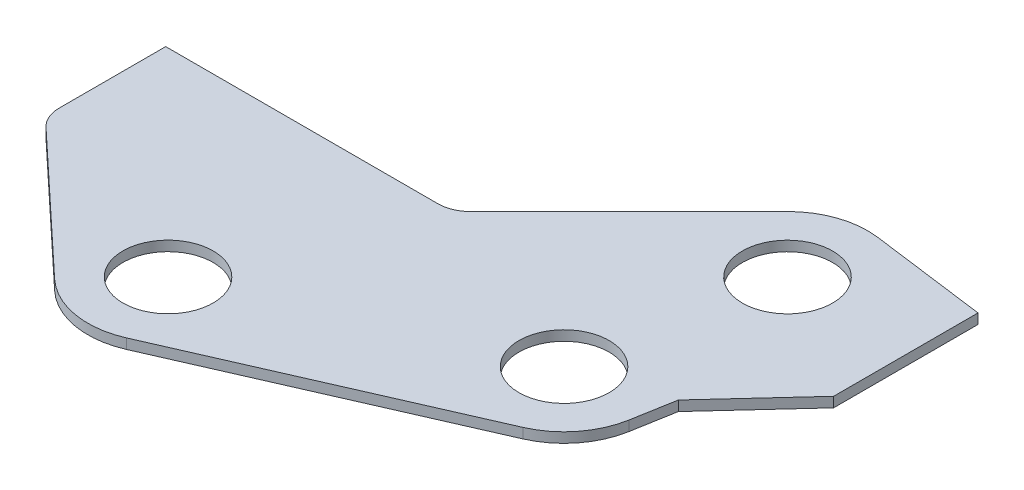
SolidWorks part; units mm, degrees
ref_plane "Front Plane" through (0, 0, 0) normal (0, 0, 1) x (1, 0, 0)
ref_plane "Top Plane" through (0, 0, 0) normal (0, 1, 0) x (1, 0, 0)
ref_plane "Right Plane" through (0, 0, 0) normal (1, 0, 0) x (0, 0, -1)
sketch "Sketch1" plane through (0, 0, 0) normal (0, 1, 0) x (1, 0, 0)
  line L1 (-62.0695, -79.8953) -> (25.163, -41.6958)
  line L5 (39.9361, -22.8907) -> (42.2711, -9.5867)
  line L6 (42.2711, -9.5867) -> (65.827, 16.0128)
  line L9 (7.8649, 59.3767) -> (-32.6636, 18.8643)
  line L12 (-135.7857, -31.9357) -> (-135.7857, 6.1643)
  line L15 (-32.6636, 18.8643) -> (-45.3687, 6.1643)
  line L16 (-135.7857, 6.1643) -> (-45.3687, 6.1643)
  line L17 (-135.7857, -31.9357) -> (-89.6201, -75.1681)
  line L20 (65.827, 16.0128) -> (65.8268, 61.7268)
  line L21 (65.8268, 61.7268) -> (29.163, 66.5919)
  circle A0 centre (25.8218, 41.4126) radius 14.29
  circle A1 centre (15.0126, -18.5165) radius 14.29
  circle A2 centre (-72.2583, -56.6285) radius 14.29
  arc A4 (39.9361, -22.8907) -> (25.163, -41.6958) centre (15.0127, -18.5164) cw
  arc A5 (7.8649, 59.3767) -> (29.163, 66.5919) centre (25.8218, 41.4126) cw
  arc A6 (-62.0695, -79.8953) -> (-89.6201, -75.1681) centre (-72.2582, -56.6283) cw
  point P11 (-62.0695, -79.8953)
extrude "Boss-Extrude1" add sketch "Sketch1" along normal blind 3.175
fillet "Fillet1" radius 10 1 edges at (-135.7857, 1.5875, 31.9357)
fillet "Fillet2" radius 10 1 edges at (-45.3687, 1.5875, -6.1643)
